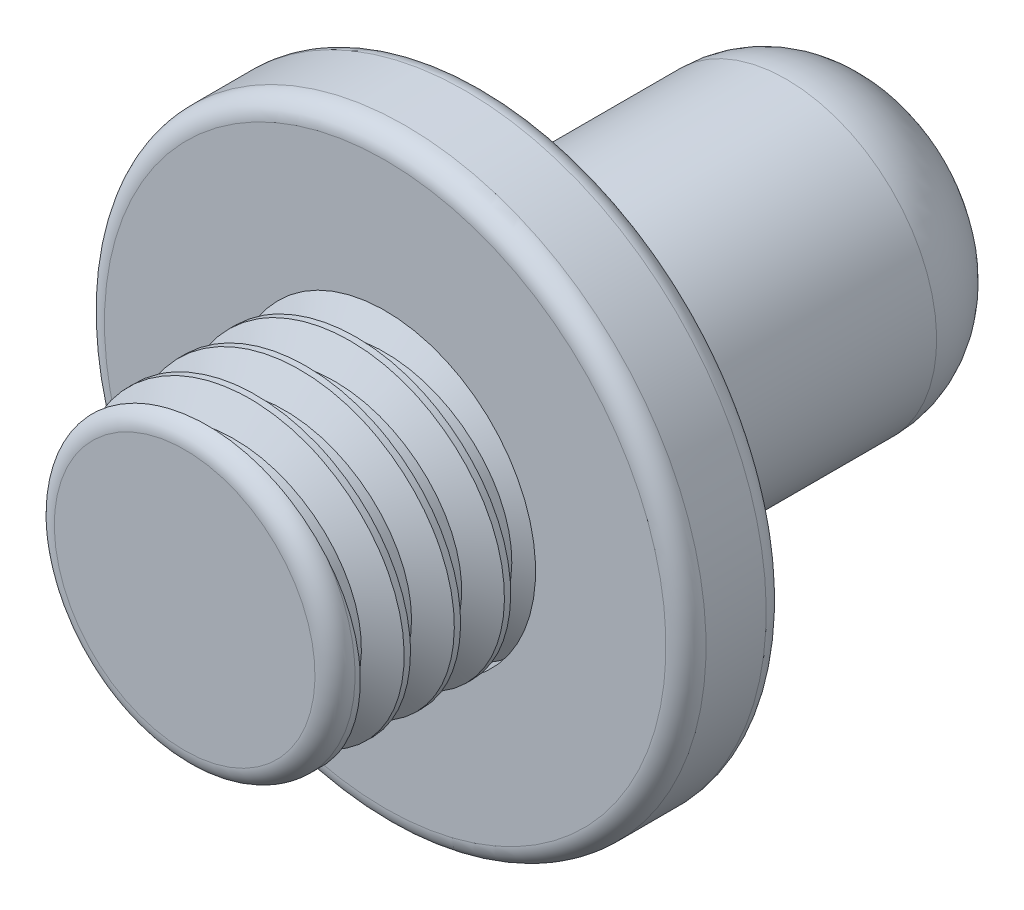
SolidWorks part; units mm, degrees
ref_plane "Front Plane" through (0, 0, 0) normal (0, 0, 1) x (1, 0, 0)
ref_plane "Top Plane" through (0, 0, 0) normal (0, 1, 0) x (1, 0, 0)
ref_plane "Right Plane" through (0, 0, 0) normal (1, 0, 0) x (0, 0, -1)
sketch "Sketch1" plane through (0, 0, 0) normal (1, 0, 0) x (0, 0, -1)
  line L0 (0, 0) -> (-7, 0)
  line L1 (-7, 0) -> (-7, 1.5)
  line L2 (-7, 1.5) -> (-5, 1.5)
  line L3 (-5, 1.5) -> (-5, 3)
  line L4 (-5, 3) -> (-4, 3)
  line L5 (-4, 3) -> (-4, 1.5)
  line L6 (-4, 1.5) -> (0, 1.5)
  line L7 (0, 1.5) -> (0, 0)
  dimension "D1" = 1
  dimension "D2" = 2
  dimension "D3" = 4
  dimension "D4" = 1.5
  dimension "D5" = 3
revolve "Revolve1" add sketch "Sketch1" angle 360 about L0
fillet "Fillet1" radius 1 1 edges at (0, 1.5, 0)
fillet "Fillet2" radius 0.2 1 edges at (0, 1.5, 7)
thread "Thread1" pitch 0.5 method cut profile "Thread Profile1" start angle 0, offset 0, length 0, pitch 0.5, diameter 3
ref_plane "Plane1" through (-1.5, 0, 7) normal (0, -1, 0) x (-1, 0, 0)
sketch "Thread Profile1" plane through (-1.5, 0, 7) normal (0, -1, 0) x (-1, 0, 0)
  line L0 (0, 0) -> (0, 0.5) construction
  line L11 (0, 0) -> (0, 0.4375)
  line L12 (0, 0.4375) -> (-0.2706, 0.2812)
  line L13 (-0.2706, 0.2812) -> (-0.2706, 0.1562)
  line L15 (-0.2706, 0.1562) -> (0, 0)
  line L17 (-0.2706, 0.2187) -> (0, 0.2187) construction
  point P2 (0, 0)
  dimension "Pitch" = 0.5
  dimension "Profile_Angle" = 60
  dimension "Profile_Land" = 0.125
  dimension "Profile_Height" = 0.2706
fillet "Fillet3" radius 0.2 2 edges at (0, 3, 4) (0, 3, 5)
